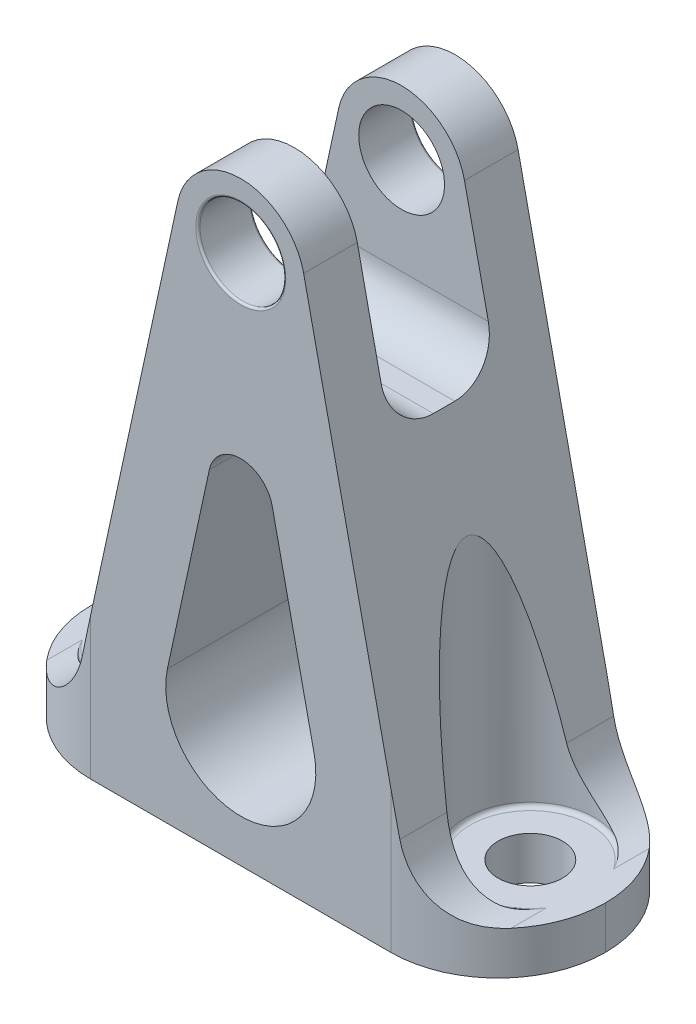
SolidWorks part; units mm, degrees
material "7075-T6, Płyta (SS)"
ref_plane "Płaszczyzna XY" through (0, 0, 0) normal (0, 0, 1) x (1, 0, 0)
ref_plane "Płaszczyzna XZ" through (0, 0, 0) normal (0, 1, 0) x (1, 0, 0)
ref_plane "Płaszczyzna YZ" through (0, 0, 0) normal (1, 0, 0) x (0, 0, -1)
sketch "Szkic1" plane through (0, 0, 0) normal (0, 0, 1) x (1, 0, 0)
  line L0 (15.559, -31) -> (63.559, -31)
  line L1 (63.559, -31) -> (63.559, -27)
  line L2 (63.559, -27) -> (48.759, 4.5)
  line L3 (48.759, 4.5) -> (48.759, 27.5)
  line L4 (48.759, 27.5) -> (30.359, 27.5)
  line L5 (30.359, 27.5) -> (30.359, 4.5)
  line L6 (30.359, 4.5) -> (15.559, -27)
  line L7 (15.559, -27) -> (15.559, -31)
  circle A0 centre (39.559, 18.5) radius 4
  dimension "D8" = 8
  dimension "D1" = 48
  dimension "D2" = 4
  dimension "D3" = 4
  dimension "D4" = 23
  dimension "D5" = 18.4
  dimension "D6" = 49.5
  dimension "D7" = 23
  dimension "D9" = 9
  dimension "D10" = 24
  dimension "D11" = 39.559
  dimension "D12" = 31
extrude "Dodanie-wyciągnięcie1" add sketch "Szkic1" along normal blind 20
sketch "Szkic2" plane through (0, 27.5, 0) normal (0, 1, 0) x (1, 0, 0)
  line L0 (53.759, -5) -> (25.359, -5)
  line L1 (25.359, -5) -> (25.359, -15)
  line L2 (25.359, -15) -> (53.759, -15)
  line L3 (53.759, -5) -> (53.759, -15)
  line L4 (48.759, 0) -> (30.359, 0) construction
  line L5 (30.359, -20) -> (30.359, 0) construction
  line L6 (48.759, -20) -> (48.759, 0) construction
  dimension "D1" = 10
  dimension "D2" = 5
  dimension "D3" = 5
  dimension "D4" = 5
extrude "Wytnij-wyciągnięcie1" cut sketch "Szkic2" against normal blind 22
sketch "Szkic3" plane through (0, 27.5, 0) normal (0, 1, 0) x (1, 0, 0)
  line L0 (15.559, -20) -> (15.559, 0) construction
  line L1 (63.559, -20) -> (63.559, 0) construction
  line L3 (48.759, 0) -> (30.359, 0) construction
  circle A0 centre (56.559, -10) radius 3
  circle A1 centre (22.559, -10) radius 3
  dimension "D1" = 6
  dimension "D2" = 6
  dimension "D3" = 7
  dimension "D4" = 7
  dimension "D5" = 10
  dimension "D6" = 10
extrude "Wytnij-wyciągnięcie2" cut sketch "Szkic3" against normal through all
sketch "Szkic4" plane through (0, 27.5, 0) normal (0, 1, 0) x (1, 0, 0)
  circle A1 centre (56.559, -10) radius 6
  circle A2 centre (22.559, -10) radius 6
  dimension "D1" = 12
  dimension "D2" = 12
extrude "Wytnij-wyciągnięcie3" cut sketch "Szkic4" against normal offset from surface (54.5 mm away) 4 up to face at (56.559, -31, 13)
sketch "Szkic6" plane through (0, 0, 0) normal (0, 0, -1) x (-1, 0, 0)
  line L0 (-63.559, -27) -> (-55.559, -27)
  line L1 (-55.559, -27) -> (-45.4229, 19.7708)
  line L2 (-15.559, -27) -> (-23.559, -27)
  line L3 (-33.6951, 19.7708) -> (-23.559, -27)
  line L4 (-63.559, -27) -> (-63.559, 33)
  line L5 (-63.559, 33) -> (-15.559, 33)
  line L6 (-15.559, 33) -> (-15.559, -27)
  arc A0 (-33.6951, 19.7708) -> (-45.4229, 19.7708) centre (-39.559, 18.5) ccw
  line M5 (-15.559, -27) -> (-30.359, 4.5)
  line M6 (-30.359, 4.5) -> (-30.359, 27.5)
  line M7 (-30.359, 27.5) -> (-48.759, 27.5)
  line M8 (-48.759, 27.5) -> (-48.759, 4.5)
  line M9 (-48.759, 4.5) -> (-63.559, -27)
  dimension "D1" = 12
  dimension "D2" = 8
  dimension "D3" = 8
  dimension "D4" = 60
extrude "Wytnij-wyciągnięcie5" cut sketch "Szkic6" against normal through all contours L0 L1 M9 | L3 L2 M5 | A0 L3 L1 M6 M7 M8 | L6 L5 L4 L1 L3 M9 M8 M7 M6 M5 region at (55.5017, -11.5588, 0) region at (62.7906, 3, 0)
fillet "Zaokrąglenie1" radius 10 4 edges at (63.559, -29, 20) (63.559, -29, 0) (15.559, -29, 20) (15.559, -29, 0)
sketch "Szkic7" plane through (0, 0, 0) normal (0, 0, -1) x (-1, 0, 0)
  line L0 (-63.559, -31) -> (-53.559, -31) construction
  line L1 (-46.4002, -18.5174) -> (-42.4909, -0.479)
  line L2 (-32.7178, -18.5174) -> (-36.6271, -0.479)
  line L6 (-53.559, -17.7715) -> (-45.4229, 19.7708) construction
  line L8 (-33.6951, 19.7708) -> (-25.559, -17.7715) construction
  arc A0 (-46.4002, -18.5174) -> (-32.7178, -18.5174) centre (-39.559, -20) ccw
  arc A1 (-36.6271, -0.479) -> (-42.4909, -0.479) centre (-39.559, -1.1145) ccw
  dimension "D1" = 14
  dimension "D2" = 6
  dimension "D3" = 11
  dimension "D4" = 24
extrude "Wytnij-wyciągnięcie6" cut sketch "Szkic7" against normal through all
fillet "Zaokrąglenie2" radius 7 4 edges at (55.559, -27, 17.857) (55.559, -27, 2.143) (23.559, -27, 17.857) (23.559, -27, 2.143)
fillet "Zaokrąglenie3" radius 4 2 edges at (39.559, 5.5, 15) (39.559, 5.5, 5)
fillet "Zaokrąglenie4" radius 0.4 2 edges at (50.559, -27, 10) (28.559, -27, 10)
fillet "Zaokrąglenie5" radius 0.2 3 edges at (43.559, 18.5, 0) (43.559, 18.5, 20) (43.559, 18.5, 15)
